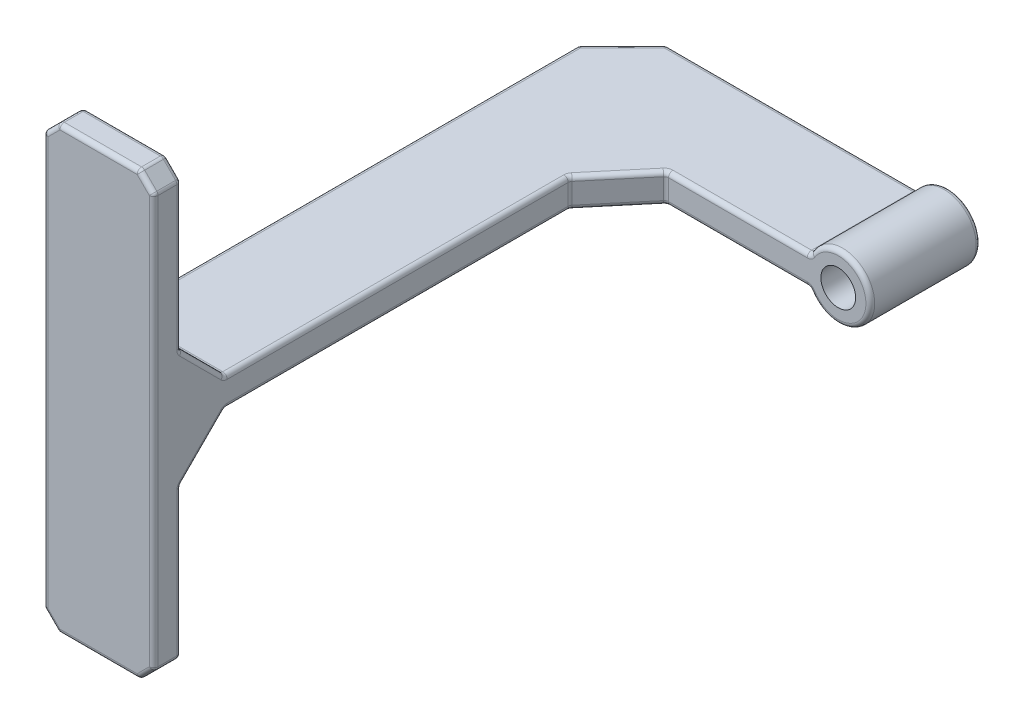
SolidWorks part; units mm, degrees
ref_plane "Front Plane" through (0, 0, 0) normal (0, 0, 1) x (1, 0, 0)
ref_plane "Top Plane" through (0, 0, 0) normal (0, 1, 0) x (1, 0, 0)
ref_plane "Right Plane" through (0, 0, 0) normal (1, 0, 0) x (0, 0, -1)
sketch "Sketch1" plane through (0, 0, 0) normal (0, 1, 0) x (1, 0, 0)
  line L0 (-25.7199, 0) -> (-25.7199, 95.25)
  line L1 (-25.7199, 95.25) -> (25.0801, 95.25)
  line L2 (25.0801, 95.25) -> (25.0801, 76.2)
  line L3 (25.0801, 76.2) -> (-6.6699, 76.2)
  line L4 (-6.6699, 76.2) -> (-6.6699, 0)
  line L5 (-6.6699, 0) -> (-25.7199, 0)
  dimension "D1" = 76.2
  dimension "D2" = 19.05
  dimension "D3" = 50.8
extrude "Boss-Extrude1" add sketch "Sketch1" along normal blind 2.54 and the other way blind 2.54
sketch "Sketch2" plane through (0, 0, 0) normal (0, 0, 1) x (1, 0, 0)
  line L0 (-6.6699, 0) -> (24.4679, 0) construction
  line L1 (-6.6699, 2.54) -> (-6.6699, -2.54) construction
  line L7 (-25.7199, 38.1) -> (-6.6699, 38.1)
  line L8 (-25.7199, 38.1) -> (-25.7199, -38.1)
  line L9 (-25.7199, -38.1) -> (-6.6699, -38.1)
  line L10 (-25.7199, -2.54) -> (-6.6699, -2.54)
  line L11 (-6.6699, -2.54) -> (-6.6699, 2.54)
  line L12 (-6.6699, 2.54) -> (-25.7199, 2.54)
  line L13 (-25.7199, 2.54) -> (-25.7199, -2.54)
  line L14 (-25.7199, -2.54) -> (-6.6699, -2.54) construction
  line L15 (-6.6699, -2.54) -> (-6.6699, 2.54) construction
  line L16 (-6.6699, 2.54) -> (-25.7199, 2.54) construction
  line L17 (-25.7199, 2.54) -> (-25.7199, -2.54) construction
  line L18 (-6.6699, 38.1) -> (-6.6699, -38.1)
  dimension "D2" = 76.2
  dimension "D1" = 0
extrude "Boss-Extrude2" add sketch "Sketch2" along normal blind 4.7625
chamfer "Chamfer1" distance 7.62 angle 45 2 edges at (-16.1949, 2.54, 0) (-16.1949, -2.54, 0)
sketch "Sketch3" plane through (0, 0, 0) normal (0, 1, 0) x (1, 0, 0)
  line L0 (25.0801, 76.2) -> (25.0801, 95.25)
  line L1 (25.0801, 76.2) -> (25.0801, 95.25)
  line L2 (27.6201, 76.2) -> (27.6201, 95.25)
  line L3 (25.0801, 76.2) -> (27.6201, 76.2)
  line L4 (25.0801, 95.25) -> (27.6201, 95.25)
  line L5 (30.6201, 76.2) -> (30.6201, 95.25) construction
  dimension "D1" = 2.54
  dimension "D2" = 3
revolve "Revolve1" add sketch "Sketch3" angle 360 about L5
sketch "Sketch4" plane through (25.0801, 0, 0) normal (1, 0, 0) x (0, 0, -1)
  line L4 (95.25, -2.54) -> (95.25, 2.54)
  line L5 (95.25, 2.54) -> (76.2, 2.54)
  line L6 (76.2, 2.54) -> (76.2, -2.54)
  line L7 (76.2, -2.54) -> (95.25, -2.54)
  line L8 (95.25, -2.54) -> (95.25, 2.54)
  line L9 (95.25, 2.54) -> (76.2, 2.54)
  line L10 (76.2, 2.54) -> (76.2, -2.54)
  line L11 (76.2, -2.54) -> (95.25, -2.54)
  dimension "D1" = 0
extrude "Boss-Extrude3" add sketch "Sketch4" along normal up to surface (0.6166 mm away) up to face at (36.1601, 0, -76.2)
chamfer "Chamfer2" distance 7.62 angle 45 1 edges at (-25.7199, 0, -95.25)
chamfer "Chamfer3" distance 7.62 angle 50 1 edges at (-6.6699, 0, -76.2) first distance on face at (12.1292, 0, -76.2)
chamfer "Chamfer4" distance 2.54 angle 45 4 edges at (-6.6699, 38.1, 2.3813) (-25.7199, 38.1, 2.3813) (-25.7199, -38.1, 2.3813) (-6.6699, -38.1, 2.3813)
fillet "Fillet2" radius 0.762 54 edges at (-9.2099, -38.1, 2.3813) (-7.9399, -36.83, 4.7625) (-16.1949, -38.1, 4.7625) (-16.1949, -38.1, 0) (-23.1799, -38.1, 2.3813) (-6.6699, -35.56, 2.3813) (-7.9399, -36.83, 0) (-7.9399, 36.83, 4.7625) (-6.6699, 0, 4.7625) (-24.4499, -36.83, 4.7625) (-16.1949, 38.1, 4.7625) (-9.2099, 38.1, 2.3813) (-25.7199, -35.56, 2.3813) (-24.4499, -36.83, 0) (-6.6699, -22.86, 0) (-6.6699, 35.56, 2.3813) (-7.9399, 36.83, 0) (-25.7199, 0, 4.7625) (-24.4499, 36.83, 4.7625) (-23.1799, 38.1, 2.3813) (-16.1949, 38.1, 0) (-16.1949, -10.16, 0) (-25.7199, -22.86, 0) (-6.6699, -6.35, -3.81) (-6.6699, 22.86, 0) (-25.7199, 35.56, 2.3813) (-24.4499, 36.83, 0) (-6.6699, -2.54, -37.3694) (-25.7199, -6.35, -3.81) (-16.1949, -2.54, -7.62) (-6.6699, 6.35, -3.81) (-16.1949, 10.16, 0) (-25.7199, 22.86, 0) (-6.6699, 2.54, -37.3694) (-6.6699, 0, -67.1188) (-2.8599, -2.54, -71.6594) (-25.7199, -2.54, -47.625) (-16.1949, 2.54, -7.62) (-25.7199, 6.35, -3.81) (0.9501, 0, -76.2) (-2.8599, 2.54, -71.6594) (13.3234, -2.54, -76.2) (-21.9099, -2.54, -91.44) (-25.7199, 0, -87.63) (-25.7199, 2.54, -47.625) (36.1601, 0, -76.2) (13.3234, 2.54, -76.2) (25.6967, -2.54, -85.725) (3.7984, -2.54, -95.25) (-18.0999, 0, -95.25) (-21.9099, 2.54, -91.44) (25.6967, 2.54, -85.725) (36.1601, 0, -95.25) (3.7984, 2.54, -95.25)
